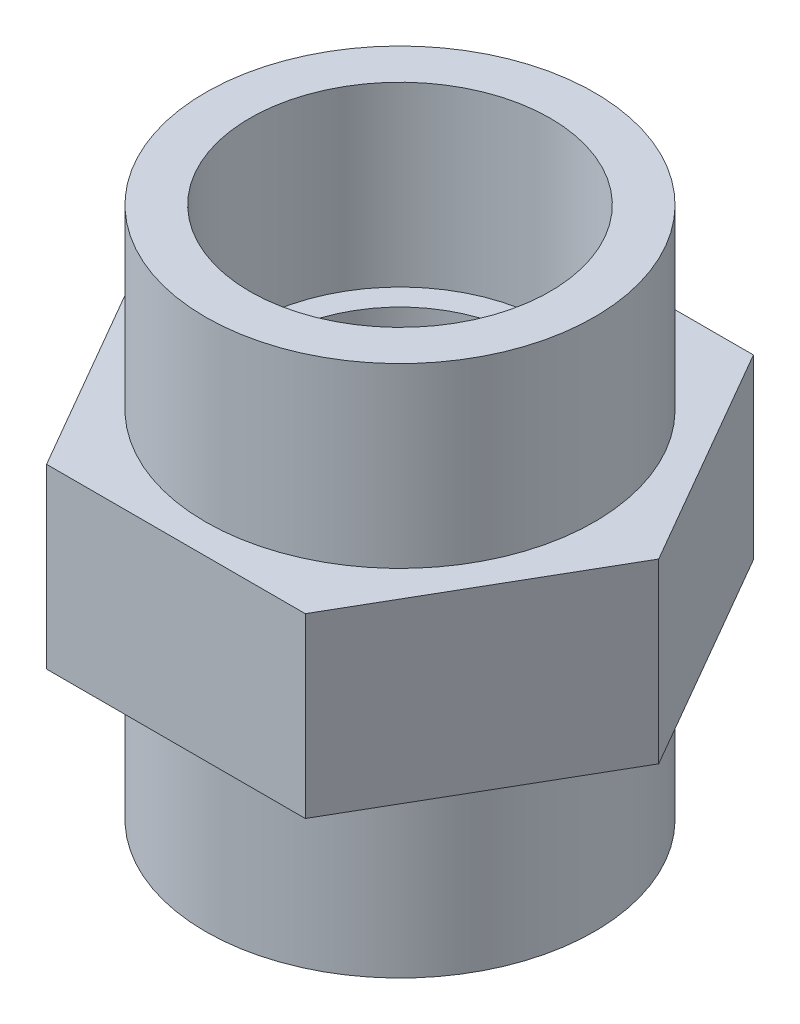
SolidWorks part; units mm, degrees
ref_plane "前视基准面" through (0, 0, 0) normal (0, 0, 1) x (1, 0, 0)
ref_plane "上视基准面" through (0, 0, 0) normal (0, 1, 0) x (1, 0, 0)
ref_plane "右视基准面" through (0, 0, 0) normal (1, 0, 0) x (0, 0, -1)
sketch "草图1" plane through (0, 0, 0) normal (0, 1, 0) x (1, 0, 0)
  line L1 (-4.3757, -7.579) -> (4.3757, -7.579)
  line L2 (4.3757, -7.579) -> (8.7515, 0)
  line L3 (8.7515, 0) -> (4.3757, 7.579)
  line L4 (4.3757, 7.579) -> (-4.3757, 7.579)
  line L5 (-4.3757, 7.579) -> (-8.7515, 0)
  line L6 (-8.7515, 0) -> (-4.3757, -7.579)
  circle A0 centre (0, 0) radius 6.579
  circle A1 centre (0, 0) radius 4.25
  circle A2 centre (0, 0) radius 7.579 construction
  dimension "A口外径" = 13.158
  dimension "六角大小" = 15.158
extrude "凸台-拉伸1" add sketch "草图1" against normal blind 6 contours A0 A1 region at (-6.3929, 0, 0)
extrude "凸台-拉伸2" add sketch "草图1<3>" along normal blind 6 contours L3 L4 L5 L6 L1 L2 | A1
sketch "草图1<3>" plane through (0, 0, 0) normal (0, 1, 0) x (1, 0, 0) same geometry as "草图1"
sketch "草图2" plane through (0, 6, 0) normal (0, 1, 0) x (1, 0, 0)
  circle A0 centre (0, 0) radius 6.579
  circle A2 centre (0, 0) radius 5.079
  dimension "B口外径" = 13.158
  dimension "D2" = 1.5
extrude "凸台-拉伸3" add sketch "草图2" along normal blind 6
